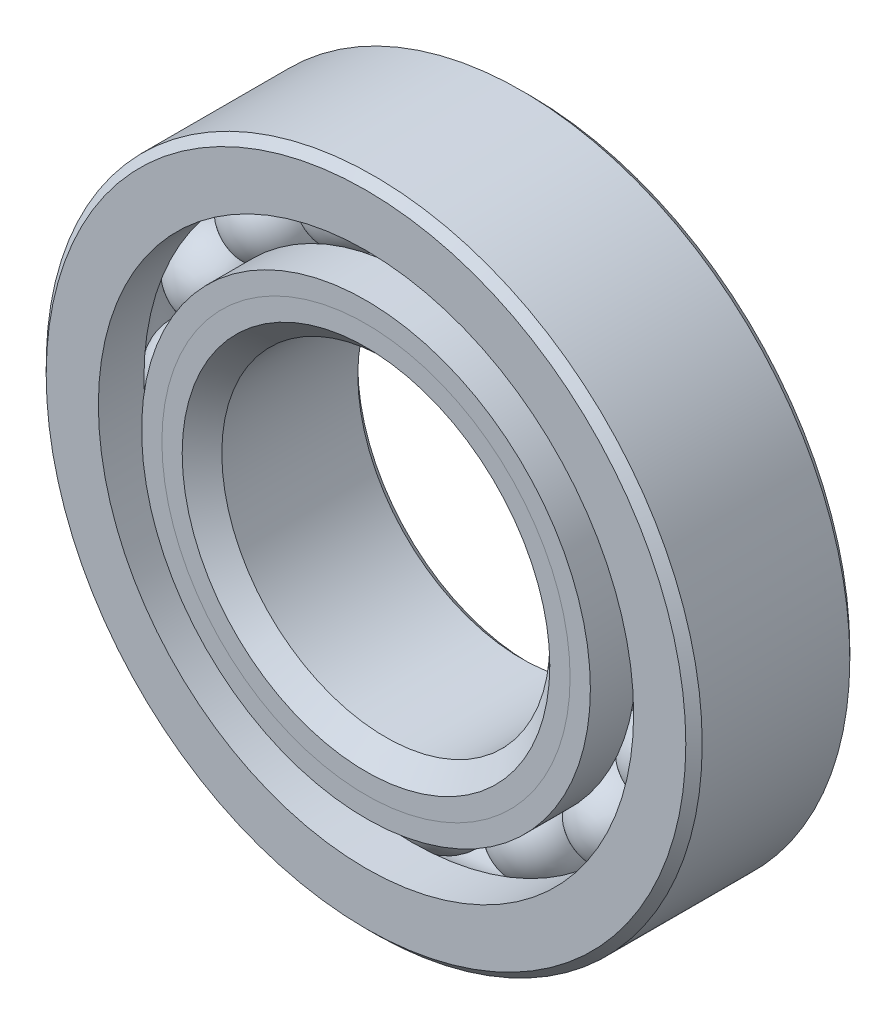
SolidWorks part; units mm, degrees
ref_plane "Front Plane" through (0, 0, 0) normal (0, 0, 1) x (1, 0, 0)
ref_plane "Top Plane" through (0, 0, 0) normal (0, 1, 0) x (1, 0, 0)
ref_plane "Right Plane" through (0, 0, 0) normal (1, 0, 0) x (0, 0, -1)
sketch "Sketch1" plane through (0, 0, 0) normal (1, 0, 0) x (0, 0, -1)
  line L0 (-6.35, 0) -> (6.35, 0) construction
  line L1 (0, 25.4) -> (0, -25.4) construction
  line L2 (5.715, 25.4) -> (-5.715, 25.4)
  line L3 (-5.715, 25.4) -> (-6.35, 24.765)
  line L4 (-6.35, 24.765) -> (-6.35, 20.7247)
  line L5 (-6.35, 20.7247) -> (-2.8222, 20.7247)
  line L6 (6.35, 20.7247) -> (2.8222, 20.7247)
  line L7 (6.35, 24.765) -> (6.35, 20.7247)
  line L8 (5.715, 25.4) -> (6.35, 24.765)
  line L9 (0, 25.4) -> (0, 19.05) construction
  line L10 (0, 19.05) -> (0, 12.7) construction
  arc A0 (-2.8222, 20.7247) -> (2.8222, 20.7247) centre (0, 19.05) cw
  point P14 (0, 12.7)
  dimension "D3" = 5.6444
  dimension "D1" = 45
  dimension "Width" = 12.7
  dimension "OD" = 50.8
  dimension "D2" = 0.635
  dimension "Shaft Dia" = 25.4
  dimension "D4" = 1.6747
revolve "Revolve1" add sketch "Sketch1" angle 360 about L0
sketch "Sketch2" plane through (0, 0, 0) normal (1, 0, 0) x (0, 0, -1)
  line L0 (-6.35, 17.3753) -> (-2.8222, 17.3753)
  line L1 (-6.35, 24.765) -> (-6.35, -24.765) construction
  line L2 (-6.35, 17.3753) -> (-6.35, 15.8047)
  line L3 (-6.35, 15.8047) -> (-4.7794, 14.2341)
  line L4 (-4.7794, 14.2341) -> (0, 14.2341)
  line L5 (0, 25.4) -> (0, -25.4) construction
  line L6 (0, 14.2341) -> (0, 15.7683)
  line L7 (0, 15.7683) -> (0, 12.7) construction
  line L8 (-6.35, 17.3753) -> (-6.35, 14.2341) construction
  line L9 (-6.35, 14.2341) -> (-4.7794, 14.2341) construction
  arc A0 (-2.8222, 17.3753) -> (0, 15.7683) centre (0, 19.05) ccw
  arc A1 (2.8222, 20.7247) -> (-2.8222, 20.7247) centre (0, 19.05) ccw construction
  circle A2 centre (0, 19.05) radius 3.2817 construction
  dimension "D1" = 45
revolve "Revolve2" add sketch "Sketch2" angle 360 about L0
sketch "Sketch3" plane through (0, 0, 0) normal (1, 0, 0) x (0, 0, -1)
  line L0 (-6.35, 15.8047) -> (-4.7794, 14.2341)
  line L1 (-4.7794, 14.2341) -> (0, 14.2341)
  line L2 (0, 14.2341) -> (0, 15.7683)
  line L3 (-6.35, 15.8047) -> (-6.35, 14.2341)
  line L4 (-6.35, 17.3753) -> (-6.35, 14.2341) construction
  line L5 (-6.35, 14.2341) -> (-4.8159, 12.7)
  line L6 (-4.8159, 12.7) -> (5.715, 12.7)
  line L7 (5.715, 25.4) -> (5.715, -25.4) construction
  line L8 (5.715, 12.7) -> (6.35, 13.335)
  line L9 (6.35, -24.765) -> (6.35, 24.765) construction
  line L10 (6.35, 13.335) -> (6.35, 17.3753)
  line L11 (6.35, 17.3753) -> (2.8222, 17.3753)
  line L13 (5.715, 25.4) -> (6.35, 24.765) construction
  circle A0 centre (0, 19.05) radius 3.2817 construction
  arc A1 (2.8222, 17.3753) -> (0, 15.7683) centre (0, 19.05) cw
revolve "Revolve3" add sketch "Sketch3" angle 360 about L0
sketch "Sketch4" plane through (0, 0, 0) normal (1, 0, 0) x (0, 0, -1)
  line L0 (-3.2817, 19.05) -> (3.2817, 19.05)
  circle A1 centre (0, 19.05) radius 3.2817 construction
  arc A2 (-3.2817, 19.05) -> (3.2817, 19.05) centre (0, 19.05) cw
  arc A3 (2.8222, 20.7247) -> (-2.8222, 20.7247) centre (0, 19.05) ccw construction
revolve "Revolve4" add sketch "Sketch4" angle 360 about L0
ref_axis "Axis1" through (0, 0, -6.35) along (0, 0, 1)
pattern_circular "CirPattern1" count 16 every 22.5 about axis through (0, 0, -6.35) along (0, 0, 1) of bodies 104
equation "\"D2@Sketch1\" = \"Width@Sketch1\"*.05"
equation "\"D3@Sketch1\" = \"Width@Sketch1\"/2.25"
equation "\"D4@Sketch1\" = (((\"OD@Sketch1\"-\"Width@Sketch1\")/2)/3.25)/3.5"
equation "\"D2@CirPattern1\" = 360/\"Balls@CirPattern1\""
